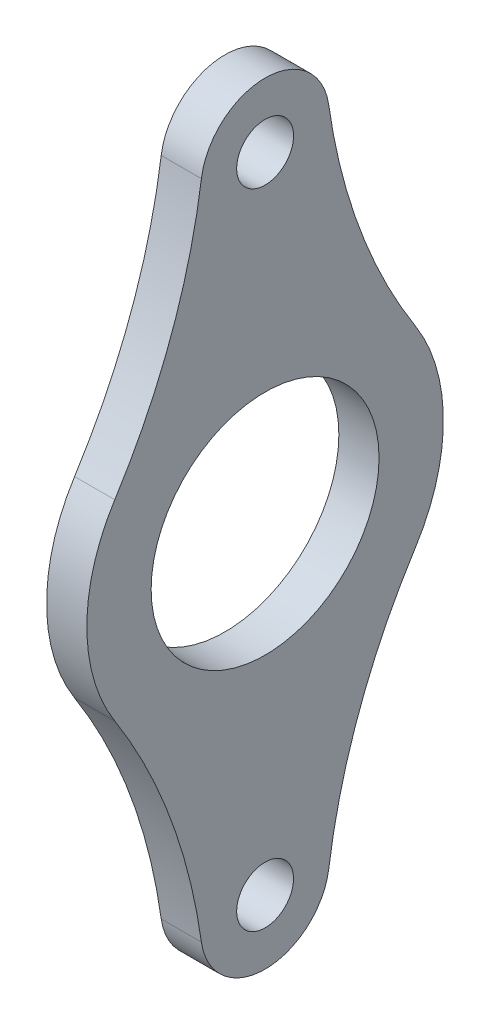
SolidWorks part; units mm, degrees
material "6061-T6 (SS)"
ref_plane "Front Plane" through (0, 0, 0) normal (0, 0, 1) x (1, 0, 0)
ref_plane "Top Plane" through (0, 0, 0) normal (0, 1, 0) x (1, 0, 0)
ref_plane "Right Plane" through (0, 0, 0) normal (1, 0, 0) x (0, 0, -1)
ref_plane "Plane1" through (54.188, 0, 0) normal (-1, 0, 0) x (0, 0, 1)
sketch "Sketch1" plane through (54.188, 0, 0) normal (-1, 0, 0) x (0, 0, 1)
  line L0 (-51.1134, 32.5835) -> (-5.0306, 26.107) construction
  line L1 (-23.0873, 0) -> (0, 0) construction
  line L2 (0, 0) -> (0, 25.4) construction
  circle A0 centre (0, -25.4) radius 2.2479 construction
  circle A1 centre (0, 25.4) radius 2.2479 construction
  circle A2 centre (0, -25.4) radius 2.2479
  circle A3 centre (0, 25.4) radius 2.2479
  circle A4 centre (0, 0) radius 9
  circle A5 centre (0, 0) radius 6 construction
  arc A6 (-11.8728, 7.5686) -> (-11.8728, -7.5686) centre (0, 0) ccw
  arc A7 (5.0306, 26.107) -> (-5.0306, 26.107) centre (0, 25.4) ccw
  arc A8 (-5.0306, -26.107) -> (5.0306, -26.107) centre (0, -25.4) ccw
  arc A9 (-5.0306, 26.107) -> (-11.8728, 7.5686) centre (-51.1134, 32.5835) cw
  arc A10 (5.0306, 26.107) -> (11.8728, 7.5686) centre (51.1134, 32.5835) ccw
  arc A11 (5.0306, -26.107) -> (11.8728, -7.5686) centre (51.1134, -32.5835) cw
  arc A12 (-5.0306, -26.107) -> (-11.8728, -7.5686) centre (-51.1134, -32.5835) ccw
  arc A13 (11.8728, -7.5686) -> (11.8728, 7.5686) centre (0, 0) ccw
  point P10 (0, 0)
  point P11 (-31.3422, 25.4)
  point P12 (-12.8687, 5.7135)
  dimension "D1" = 18
  dimension "D2" = 12
  dimension "D4" = 10.16
  dimension "D3" = 5.08
  dimension "D5" = 8
extrude "Boss-Extrude1" add sketch "Sketch1" along normal blind 3.175
equation "\"D1@Sketch1\"=18mm"
equation "\"D2@Sketch1\"=12mm"
